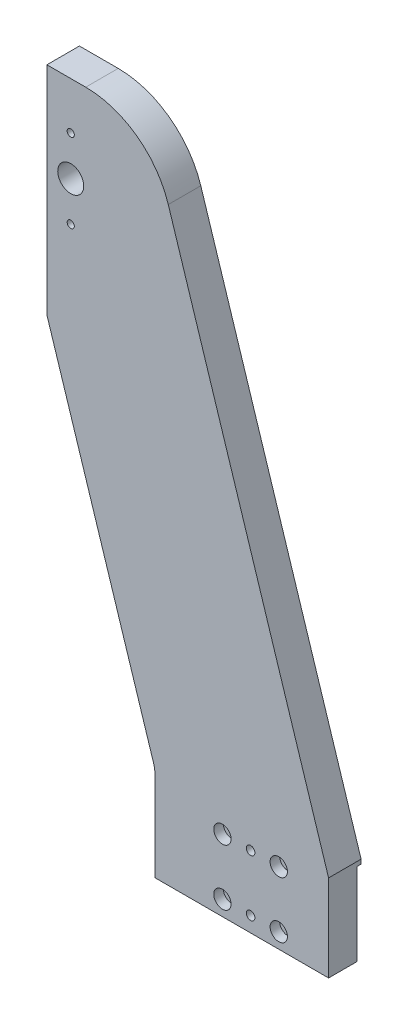
SolidWorks part; units mm, degrees
material "3.3547 (EN-AW 5083)"
ref_plane "Alzado" through (0, 0, 0) normal (0, 0, 1) x (1, 0, 0)
ref_plane "Planta" through (0, 0, 0) normal (0, 1, 0) x (1, 0, 0)
ref_plane "Vista lateral" through (0, 0, 0) normal (1, 0, 0) x (0, 0, -1)
sketch "Croquis1" plane through (0, 0, 0) normal (0, 0, 1) x (1, 0, 0)
  line L0 (80, 0) -> (80, 40)
  line L1 (-50, 300) -> (-32.095, 300)
  line L2 (-50, 300) -> (-50, 200)
  line L3 (0, 0) -> (80, 0)
  line L4 (6.0164, 272.1459) -> (80, 40)
  line L9 (-50, 200) -> (-0.9443, 46.0729)
  line L11 (0, 40) -> (0, 0)
  arc A2 (6.0164, 272.1459) -> (-32.095, 300) centre (-32.095, 260) ccw
  arc A3 (0, 40) -> (-0.9443, 46.0729) centre (-20, 40) ccw
  point P14 (0, 43.1099)
  dimension "D7" = 20
  dimension "D9" = 40
  dimension "D1" = 40
  dimension "D2" = 300
  dimension "D3" = 80
  dimension "D4" = 50
  dimension "D5" = 100
  dimension "D6" = 40
extrude "Saliente-Extruir1" add sketch "Croquis1" along normal blind 15
sketch "Croquis2" plane through (0, 0, 0) normal (0, 0, -1) x (-1, 0, 0)
  line L0 (32.095, 300) -> (50, 300) construction
  line L2 (50, 300) -> (50, 200) construction
  circle A0 centre (39, 260) radius 6
  dimension "D3" = 12
  dimension "D1" = 40
  dimension "D2" = 11
extrude "Cortar-Extruir1" cut sketch "Croquis2" against normal through all
hole_wizard "Perforador para roscar para macho de roscar para M44" positions "Croquis7" profile "Croquis8" hole size "M4" standard "DIN"
sketch "Croquis7" plane through (0, 0, 15) normal (0, 0, 1) x (1, 0, 0)
  line L0 (-39, 278.25) -> (-39, 241.75)
  circle A0 centre (-39, 260) radius 6 construction
  point P1 (-39, 278.25)
  point P2 (-39, 241.75)
  dimension "D1" = 18.25
  dimension "D2" = 18.25
sketch "Croquis8" plane through (-39, 278.25, 15) normal (1, 0, 0) x (0, -1, 0)
  line L0 (0, 0) -> (0, 7.9914)
  line L1 (0, 7.9914) -> (1.65, 7)
  line L2 (1.65, 7) -> (1.65, 0)
  line L5 (1.65, 0) -> (0, 0)
  line L10 (0, 7.9914) -> (-1.65, 7) construction
  line L11 (0, -6.35) -> (0, 107.95) construction
  dimension "Diámetro de taladro" = 3.3
  dimension "Profundidad de taladro" = 7
  dimension "Ángulo de perforador" = 118
sketch "Croquis9" plane through (0, 0, 0) normal (0, 0, -1) x (-1, 0, 0)
  line L1 (0, 0) -> (-80, 0)
  line L2 (0, 0) -> (0, 38)
  line L3 (0, 38) -> (-80, 38)
  line L4 (-80, 0) -> (-80, 38)
  dimension "D1" = 80
  dimension "D2" = 38
extrude "Cortar-Extruir2" cut sketch "Croquis9" against normal blind 2
hole_wizard "Perforador para roscar para macho de roscar para M45" positions "Croquis10" profile "Croquis11" hole size "M4" standard "DIN"
sketch "Croquis10" plane through (-50, 0, 0) normal (-1, 0, 0) x (0, 0, 1)
  line L0 (15, 300) -> (0, 300) construction
  line L1 (15, 300) -> (15, 200) construction
  point P0 (9, 285)
  point P2 (9, 235)
  dimension "D1" = 15
  dimension "D2" = 65
  dimension "D3" = 6
  dimension "D4" = 6
sketch "Croquis11" plane through (-50, 285, 9) normal (0, 1, 0) x (0, 0, 1)
  line L0 (0, 0) -> (0, 15.9914)
  line L1 (0, 15.9914) -> (1.65, 15)
  line L2 (1.65, 15) -> (1.65, 0)
  line L5 (1.65, 0) -> (0, 0)
  line L10 (0, 15.9914) -> (-1.65, 15) construction
  line L11 (0, -6.35) -> (0, 107.95) construction
  dimension "Diámetro de taladro" = 3.3
  dimension "Profundidad de taladro" = 15
  dimension "Ángulo de perforador" = 118
hole_wizard "Taladros de espiga de Ø4.0mm1" positions "Croquis12" profile "Croquis13" hole size "Ø4.0" standard "DIN"
sketch "Croquis12" plane through (-50, 0, 0) normal (-1, 0, 0) x (0, 0, 1)
  line L0 (15, 300) -> (0, 300) construction
  line L1 (15, 300) -> (15, 200) construction
  point P0 (9, 274)
  point P2 (9, 246)
  dimension "D1" = 26
  dimension "D2" = 54
  dimension "D3" = 6
  dimension "D4" = 6
sketch "Croquis13" plane through (-50, 274, 9) normal (0, 1, 0) x (0, 0, 1)
  line L0 (0, 0) -> (0, 18.2017)
  line L1 (0, 18.2017) -> (2, 17)
  line L2 (2, 17) -> (2, 0)
  line L5 (2, 0) -> (0, 0)
  line L10 (0, 18.2017) -> (-2, 17) construction
  line L11 (0, -6.35) -> (0, 107.95) construction
  dimension "Diámetro de taladro" = 4
  dimension "Profundidad de taladro" = 17
  dimension "Ángulo de perforador" = 118
hole_wizard "Taladros de espiga de Ø4.0mm3" positions "Croquis14" profile "Croquis15" hole size "Ø4.0" standard "DIN" end condition through all
sketch "Croquis14" plane through (0, 0, 15) normal (0, 0, 1) x (1, 0, 0)
  line L0 (44, 33) -> (44, 7) construction
  line L3 (0, 0) -> (80, 0) construction
  line L4 (80, 0) -> (80, 40) construction
  point P1 (44, 33)
  point P2 (44, 7)
  dimension "D1" = 26
  dimension "D2" = 7
  dimension "D3" = 36
sketch "Croquis15" plane through (44, 33, 15) normal (1, 0, 0) x (0, -1, 0)
  line L0 (0, 0) -> (0, 15)
  line L1 (0, 15) -> (2, 15)
  line L2 (2, 15) -> (2, 0)
  line L5 (2, 0) -> (0, 0)
  line L11 (0, -6.35) -> (0, 107.95) construction
  dimension "Diámetro de taladro hasta el siguiente" = 4
  dimension "Profundidad de taladro hasta el siguiente" = 15
hole_wizard "Refrentado para tornillo con cabeza hueca de M41" positions "Croquis16" profile "Croquis17" counterbore size "M4" standard "DIN" end condition through all
sketch "Croquis16" plane through (0, 0, 15) normal (0, 0, 1) x (1, 0, 0)
  line L1 (31, 7) -> (57, 7)
  line L2 (31, 7) -> (31, 33)
  line L3 (31, 33) -> (57, 33)
  line L4 (57, 7) -> (57, 33)
  line L5 (31, 7) -> (57, 33) construction
  line L6 (31, 33) -> (57, 7) construction
  line L7 (0, 0) -> (80, 0) construction
  line L8 (80, 0) -> (80, 40) construction
  point P2 (57, 33)
  point P135 (31, 7)
  point P136 (31, 33)
  point P137 (57, 7)
  dimension "D1" = 26
  dimension "D2" = 26
  dimension "D3" = 7
  dimension "D4" = 23
sketch "Croquis17" plane through (57, 33, 15) normal (1, 0, 0) x (0, -1, 0)
  line L0 (0, 0) -> (0, 15)
  line L1 (0, 15) -> (2.25, 15)
  line L3 (2.25, 15) -> (2.25, 4.4)
  line L4 (2.25, 4.4) -> (4, 4.4)
  line L5 (4, 4.4) -> (4, 0)
  line L7 (4, 0) -> (0, 0)
  line L11 (0, -6.35) -> (0, 107.95) construction
  dimension "Diámetro de taladro hasta el siguiente" = 4.5
  dimension "Profundidad de taladro hasta el siguiente" = 15
  dimension "Diámetro de refrentado" = 8
  dimension "Profundidad de refrentado" = 4.4
